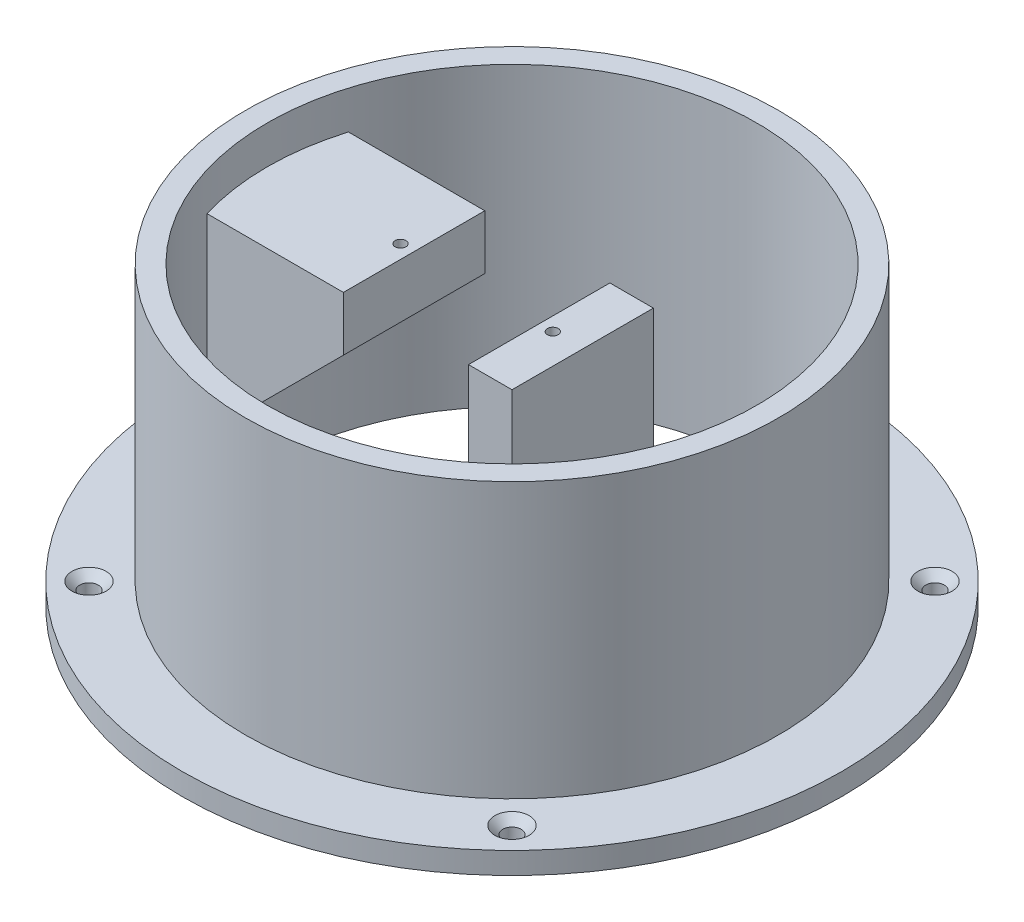
SolidWorks part; units mm, degrees
ref_plane "Front Plane" through (0, 0, 0) normal (0, 0, 1) x (1, 0, 0)
ref_plane "Top Plane" through (0, 0, 0) normal (0, 1, 0) x (1, 0, 0)
ref_plane "Right Plane" through (0, 0, 0) normal (1, 0, 0) x (0, 0, -1)
sketch "Sketch1" plane through (0, 0, 0) normal (0, 1, 0) x (1, 0, 0)
  circle A0 centre (0, 0) radius 60.625
  circle A1 centre (0, 0) radius 45
  dimension "D1" = 121.25
  dimension "D2" = 90
extrude "Boss-Extrude1" add sketch "Sketch1" along normal blind 4
sketch "Sketch2" plane through (0, 4, 0) normal (0, 1, 0) x (1, 0, 0)
  circle A0 centre (0, 0) radius 45 construction
  circle A1 centre (0, 0) radius 45
  circle A2 centre (0, 0) radius 49
  dimension "D1" = 4
extrude "Boss-Extrude2" add sketch "Sketch2" along normal blind 50.5
ref_plane "Plane1" through (0, 34.5, 0) normal (0, 1, 0) x (1, 0, 0)
sketch "Sketch4" plane through (0, 0, 0) normal (0, 0, 1) x (1, 0, 0)
  line L0 (-60.625, 0) -> (60.625, 0) construction
  line L1 (5, 47.5) -> (13, 47.5)
  line L2 (5, 47.5) -> (5, 0)
  line L3 (5, 0) -> (13, 0)
  line L4 (13, 47.5) -> (13, 0)
  line L5 (49, 54.5) -> (-49, 54.5) construction
  line L6 (-45, 54.5) -> (-45, 4)
  line L7 (-18, 47.5) -> (-45, 47.5)
  line L8 (-18, 47.5) -> (-18, 37.5)
  line L9 (-18, 37.5) -> (-45, 37.5)
  line L10 (-45, 47.5) -> (-45, 37.5)
  line L11 (60.625, 4) -> (-60.625, 4) construction
  line L12 (-18, 37.5) -> (-45, 10.5)
  dimension "D1" = 5
  dimension "D2" = 8
  dimension "D3" = 7
  dimension "D4" = 23
  dimension "D5" = 27
  dimension "D6" = 10
  dimension "D7" = 45
  dimension "D8" = 7
extrude "Boss-Extrude4" add sketch "Sketch4" along normal mid plane 26 contours L9 L8 L7 L6 | L12 L9 L6 | L1 L4 L3 L2 region at (-31.5, 42.5, 0) region at (-36, 28.5, 0)
sketch "Sketch5" plane through (0, 0, 0) normal (0, -1, 0) x (1, 0, 0)
  line L0 (3.3931, 14.5721) -> (34.8417, 28.479)
  line L1 (3.3931, -12.7877) -> (35.3292, -27.872)
  line L2 (3.3931, 14.5721) -> (3.3931, -12.7877)
  circle A0 centre (0, 0) radius 45 construction
  arc A1 (35.3292, -27.872) -> (34.8417, 28.479) centre (0, 0) ccw
extrude "Boss-Extrude5" add sketch "Sketch5" against normal up to surface (4 mm away) contours L0 A1 L1 L2 up to face at (0, 4, 60.625)
sketch "Sketch7" plane through (0, 47.5, 0) normal (0, 1, 0) x (1, 0, 0)
  line L0 (-18, -13) -> (-18, 13) construction
  circle A0 centre (-20.5, 5) radius 1.3
  circle A1 centre (-20.5, -5) radius 1.3
  circle A2 centre (27.5, 5) radius 1.3
  circle A3 centre (27.5, -5) radius 1.3
  dimension "D1" = 2.6
  dimension "D2" = 2.6
  dimension "D3" = 10
  dimension "D4" = 5
  dimension "D5" = 2.5
  dimension "D7" = 48
  dimension "D6" = 2
sketch "Sketch12" plane through (0, 4, 0) normal (0, 1, 0) x (1, 0, 0)
  line L3 (11.3931, 7.7188) -> (11.3931, -9.3624)
  line L4 (11.3931, 7.7188) -> (11.3931, -9.3624)
  line L9 (18, 10.8394) -> (18, -12.2841)
  line L10 (13, -13) -> (13, 13) construction
  line L18 (11.3931, -9.3624) -> (32.0457, -18.4953)
  line L19 (32.4985, 17.6875) -> (11.3931, 7.7188)
  line L21 (18, -12.2841) -> (32.0457, -18.4953)
  line L22 (32.4985, 17.6875) -> (18, 10.8394)
  arc A2 (32.0457, -18.4953) -> (32.4985, 17.6875) centre (0, 0) ccw
  arc A3 (32.0457, -18.4953) -> (32.4985, 17.6875) centre (0, 0) ccw
  dimension "D2" = 5
  dimension "D1" = 8
extrude "Cut-Extrude9" cut sketch "Sketch12" against normal through all contours L21 A3 L22 | L22 L9 L21 region at (27.4858, 4, 0.4769)
sketch "Sketch14" plane through (0, 4, 0) normal (0, 1, 0) x (1, 0, 0)
  line L0 (0, 0) -> (-38.8909, 38.8909) construction
  line L1 (5, 13) -> (13, 13) construction
  circle A0 centre (-38.8909, 38.8909) radius 1.5
  circle A1 centre (38.8909, 38.8909) radius 1.5
  circle A2 centre (38.8909, -38.8909) radius 1.5
  circle A3 centre (-38.8909, -38.8909) radius 1.5
  point P15 (0, 0)
  dimension "D1" = 3
  dimension "D2" = 55
  dimension "D3" = 135
  dimension "D4" = 4
hole_wizard "CSK for M3 Countersunk Flat Head Screw1" positions "Sketch15" profile "Sketch17" countersink size "M3" standard "DIN" end condition up to next
sketch "Sketch15" plane through (0, 4, 0) normal (0, 1, 0) x (1, 0, 0)
  point P0 (-38.8909, 38.8909)
  point P3 (-38.8909, -38.8909)
  point P6 (38.8909, -38.8909)
  point P9 (38.8909, 38.8909)
sketch "Sketch17" plane through (-38.8909, 4, -38.8909) normal (1, 0, 0) x (0, 0, 1)
  line L0 (0, 0) -> (0, 4)
  line L1 (0, 4) -> (1.7, 4)
  line L2 (1.7, 4) -> (1.7, 1.45)
  line L3 (1.7, 1.45) -> (3.15, 0)
  line L5 (3.15, 0) -> (0, 0)
  line L6 (-1.7, 1.45) -> (-3.15, 0) construction
  line L11 (0, -6.35) -> (0, 107.95) construction
  dimension "Thru Hole Dia." = 3.4
  dimension "Thru Hole Depth" = 4
  dimension "Near C'Sink Dia." = 6.3
  dimension "Near C'Sink Angle" = 90
sketch "Sketch18" plane through (0, 47.5, 0) normal (0, 1, 0) x (1, 0, 0)
  line L0 (-18, -13) -> (-18, 13) construction
  line L1 (5, -13) -> (5, 13) construction
  circle A0 centre (-20.5, 0) radius 1
  circle A1 centre (7.5, 0) radius 1
  point P4 (-18, 0)
  dimension "D1" = 2.5
  dimension "D2" = 2.5
extrude "Cut-Extrude10" cut sketch "Sketch18" against normal blind 4.5 contours A0
extrude "Cut-Extrude11" cut sketch "Sketch18<3>" against normal blind 4.5
sketch "Sketch18<3>" plane through (0, 47.5, 0) normal (0, 1, 0) x (1, 0, 0) same geometry as "Sketch18"
